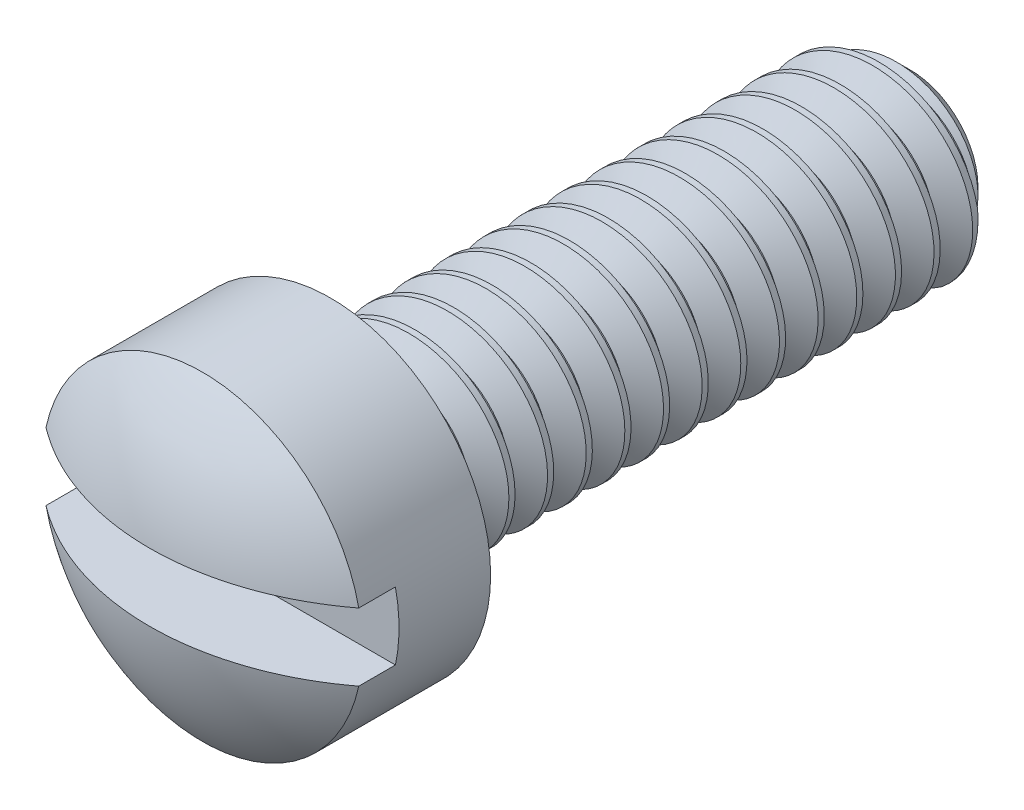
SolidWorks part; units mm, degrees
ref_plane "Front" through (0, 0, 0) normal (0, 0, 1) x (1, 0, 0)
ref_plane "Top" through (0, 0, 0) normal (0, 1, 0) x (1, 0, 0)
ref_plane "Right" through (0, 0, 0) normal (1, 0, 0) x (0, 0, -1)
sketch "Sketch1" plane through (0, 0, 0) normal (0, 0, 1) x (1, 0, 0)
  circle A0 centre (0, 0) radius 5.2578
  dimension "Head Dia" = 10.5156
extrude "Extrude3" add sketch "Sketch1" along normal blind 6.0198
sketch "Sketch11" plane through (0, 0, 0) normal (1, 0, 0) x (0, 0, -1)
  line L0 (0, 0) -> (-6.2738, 0) construction
  line L4 (-6.0198, 5.2578) -> (-6.0198, -5.2578) construction
  line L5 (-6.2738, 5.4681) -> (0, 5.4681)
  line L7 (0, 5.4681) -> (0, 5.2578)
  line L8 (-4.2139, 5.2578) -> (0, 5.2578)
  line L9 (0, -5.2578) -> (0, 5.2578) construction
  line L13 (-6.0198, 0) -> (-6.2738, 0)
  line L14 (-6.2738, 0) -> (-6.2738, 5.4681)
  arc A0 (-4.2139, 5.2578) -> (-6.0198, 0) centre (2.5369, 0) ccw
  dimension "D3" = 0.254
  dimension "D5" = 0.2103
  dimension "D2" = 1.8059
revolve "Cut-Revolve3" cut sketch "Sketch11" angle 360 about L0
sketch "Sketch4" plane through (0, 0, 0) normal (1, 0, 0) x (0, 0, -1)
  line L0 (0, 0) -> (19.05, 0)
  line L3 (19.05, 0) -> (19.05, 3.175)
  line L4 (19.05, 3.175) -> (0, 3.175)
  line L6 (0, 3.175) -> (0, 0)
  line L9 (19.05, 3.175) -> (19.05, -3.175) construction
  dimension "length" = 19.05
  dimension "dia" = 6.35
revolve "Revolve1" add sketch "Sketch4" angle 360 about L0
sketch "Sketch13" plane through (0, 0, -19.05) normal (0, 0, -1) x (-1, 0, 0)
  circle A2 centre (0, 0) radius 3.175
curve "Helix/Spiral1" pitch 1.27 height 25.0698 radius 3.175 centre (0, 0, -19.05) axis (0, 0, 1) start towards (1, 0, 0)
chamfer "Chamfer2" distance 0.9525 angle 45 1 edges at (3.175, 0, -19.05)
sketch "Sketch14" plane through (0, 0, 0) normal (1, 0, 0) x (0, 0, -1)
  line L0 (19.05, 3.2147) -> (20.1613, 3.2147)
  line L1 (20.1613, 3.2147) -> (19.685, 2.3555)
  line L2 (19.685, 2.3555) -> (19.5263, 2.3555)
  line L3 (19.5263, 2.3555) -> (19.05, 3.2147)
  line L4 (19.2881, 2.7851) -> (19.9231, 2.7851) construction
  dimension "D1" = 0.1588
  dimension "D2" = 58
  dimension "D3" = 0.635
  dimension "D4" = 0.0397
sweep "Cut-Sweep1" cut profiles "Sketch14" path "Helix/Spiral1" align with end faces yes
ref_plane "Plane1" through (0, 0, 19.05) normal (0, 0, -1) x (-1, 0, 0)
sketch "Sketch29" [suppressed] plane through (0, 0, 28.575) normal (0, 0, -1) x (-1, 0, 0)
  circle A0 centre (0, 0) radius 1.7526 construction
  circle A1 centre (0, 0) radius 1.7526
  point P3 (0, -1.7526)
  point P4 (0, 1.7526)
extrude "Extrude11" [suppressed] add sketch "Sketch29" against normal up to surface (28.575 mm away) up to plane "Front"
ref_plane "Plane2" through (0, 0, 6.0198) normal (0, 0, 1) x (1, 0, 0)
sketch "Sketch26" plane through (0, 0, 0) normal (0, 0, 1) x (1, 0, 0)
  circle A1 centre (0, 0) radius 0.5461
  dimension "D1" = 1.0922
extrude "Extrude13" add sketch "Sketch26" along normal up to surface (6.0024 mm away)
sketch "Sketch31" plane through (0, 0, 6.0198) normal (0, 0, 1) x (1, 0, 0)
  line L0 (-5.2578, 1.1113) -> (5.2578, -1.1112) construction
  line L1 (-5.2578, 1.1113) -> (5.2578, 1.1113)
  line L2 (-5.2578, 1.1113) -> (-5.2578, -1.1113)
  line L3 (-5.2578, -1.1113) -> (5.2578, -1.1112)
  line L4 (5.2578, 1.1113) -> (5.2578, -1.1112)
  circle A0 centre (0, 0) radius 5.2578 construction
  dimension "D1" = 2.2225
extrude "Extrude15" cut sketch "Sketch31" against normal blind 3.0099
sketch "Sketch18" plane through (0, 0, 0) normal (1, 0, 0) x (0, 0, -1)
  line L1 (19.05, 3.175) -> (0, 3.175) construction
  point P0 (17.145, -3.175)
  point P1 (17.78, 3.175)
  point P2 (-6.0198, 1.1113)
  dimension "D1" = 1.27
  dimension "D2" = 1.905
equation "\"D3@Helix/Spiral1\" = \"length@Sketch4\" + \"Head Ht@Extrude3\""
equation "\"D1@Sketch14\" = \"D4@Helix/Spiral1\" * .125"
equation "\"D3@Sketch14\" = \"D4@Helix/Spiral1\" * .5"
equation "\"D5@Sketch11\" = \"Head Dia@Sketch1\" * .02"
equation "\"D4@Sketch14\" = \"D1@Sketch14\" * .25"
equation "\"D1@Chamfer2\" = \"D4@Helix/Spiral1\" * .75"
equation "\"D1@Sketch18\" = \"D4@Helix/Spiral1\""
equation "\"D2@Sketch18\" = \"D4@Helix/Spiral1\" * 1.5"
equation "\"D1@Extrude15\" = \"Head Ht@Extrude3\" * .5"
equation "\"D2@Sketch11\" = \"Head Ht@Extrude3\" * .3"
equation "\"D1@Sketch31\" = \"D4@Helix/Spiral1\" * 1.75"
